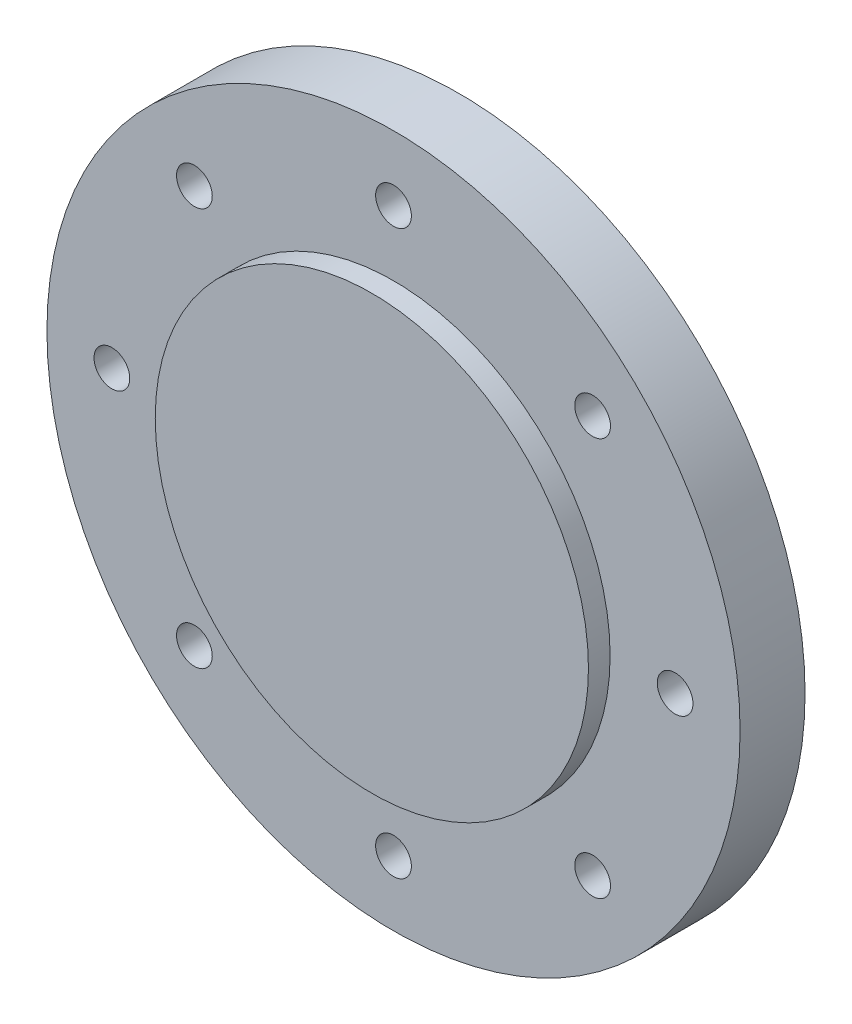
SolidWorks part; units mm, degrees
ref_plane "Front Plane" through (0, 0, 0) normal (0, 0, 1) x (1, 0, 0)
ref_plane "Top Plane" through (0, 0, 0) normal (0, 1, 0) x (1, 0, 0)
ref_plane "Right Plane" through (0, 0, 0) normal (1, 0, 0) x (0, 0, -1)
sketch "SK_Disc" plane through (0, 0, 0) normal (0, 0, 1) x (1, 0, 0)
  circle A0 centre (0, 0) radius 32
  dimension "D_disc" = 64
extrude "Output_Disc" add sketch "SK_Disc" along normal blind 6
ref_plane "PL_Mount" through (0, 0, 6) normal (0, 0, 1) x (1, 0, 0)
sketch "SK_Pilot" plane through (0, 0, 6) normal (0, 0, 1) x (1, 0, 0)
  circle A0 centre (0, 0) radius 20
  dimension "D_pil" = 40
extrude "Pilot_Boss" add sketch "SK_Pilot" along normal blind 2
sketch "SK_OutHole" plane through (0, 0, 6) normal (0, 0, 1) x (1, 0, 0)
  circle A0 centre (26, 0) radius 1.65
  dimension "D_oh" = 3.3
  dimension "R_oh" = 26
extrude "Output_Tapped_Hole" cut sketch "SK_OutHole" against normal blind 6
ref_axis "AX_Joint" through (0, 0, -0.4) along (0, 0, 1)
pattern_circular "Output_Hole_Pattern" count 8 over 360 about axis through (0, 0, -0.4) along (0, 0, 1) of "Output_Tapped_Hole"
equation "\"D_out\" = 64"
equation "\"T_out\" = 6"
equation "\"PCD_out\" = 52"
equation "\"D_pilot\" = 40"
equation "\"H_pilot\" = 2"
equation "\"D_out_hole\" = 3.3"
equation "\"D_disc@SK_Disc\" = \"D_out\""
equation "\"D1@Output_Disc\" = \"T_out\""
equation "\"D_pil@SK_Pilot\" = \"D_pilot\""
equation "\"D1@Pilot_Boss\" = \"H_pilot\""
equation "\"D_oh@SK_OutHole\" = \"D_out_hole\""
equation "\"R_oh@SK_OutHole\" = \"PCD_out\"/2"
